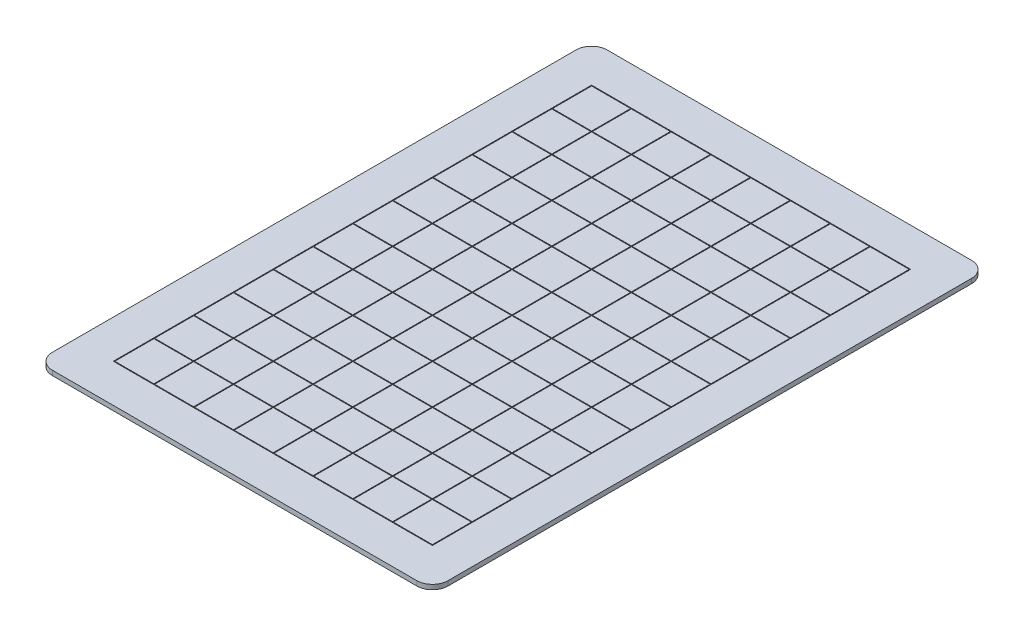
SolidWorks part; units mm, degrees
ref_plane "Front Plane" through (0, 0, 0) normal (0, 0, 1) x (1, 0, 0)
ref_plane "Top Plane" through (0, 0, 0) normal (0, 1, 0) x (1, 0, 0)
ref_plane "Right Plane" through (0, 0, 0) normal (1, 0, 0) x (0, 0, -1)
sketch "Sketch1" plane through (0, 0, 0) normal (0, 1, 0) x (1, 0, 0)
  line L1 (0, 0) -> (253.5, 0)
  line L2 (0, 0) -> (0, 355.5)
  line L3 (0, 355.5) -> (253.5, 355.5)
  line L4 (253.5, 0) -> (253.5, 355.5)
  dimension "D1" = 253.5
  dimension "D2" = 355.5
extrude "Boss-Extrude1" add sketch "Sketch1" along normal blind 3
sketch "Sketch2" plane through (0, 3, 0) normal (0, 1, 0) x (1, 0, 0)
  line L0 (0, 0) -> (253.5, 0) construction
  line L1 (25, 50) -> (50, 50)
  line L2 (25, 50) -> (25, 25)
  line L3 (25, 25) -> (50, 25)
  line L4 (50, 50) -> (50, 25)
  line L5 (0, 355.5) -> (0, 0) construction
  line L6 (50.5, 50) -> (50.5, 25)
  line L7 (50.5, 50) -> (75.5, 50)
  line L8 (75.5, 50) -> (75.5, 25)
  line L9 (50.5, 25) -> (75.5, 25)
  line L10 (76, 50) -> (76, 25)
  line L11 (76, 50) -> (101, 50)
  line L12 (101, 50) -> (101, 25)
  line L13 (76, 25) -> (101, 25)
  line L14 (101.5, 50) -> (101.5, 25)
  line L15 (101.5, 50) -> (126.5, 50)
  line L16 (126.5, 50) -> (126.5, 25)
  line L17 (101.5, 25) -> (126.5, 25)
  line L18 (127, 50) -> (127, 25)
  line L19 (127, 50) -> (152, 50)
  line L20 (152, 50) -> (152, 25)
  line L21 (127, 25) -> (152, 25)
  line L22 (152.5, 50) -> (152.5, 25)
  line L23 (152.5, 50) -> (177.5, 50)
  line L24 (177.5, 50) -> (177.5, 25)
  line L25 (152.5, 25) -> (177.5, 25)
  line L26 (178, 50) -> (178, 25)
  line L27 (178, 50) -> (203, 50)
  line L28 (203, 50) -> (203, 25)
  line L29 (178, 25) -> (203, 25)
  line L30 (203.5, 50) -> (203.5, 25)
  line L31 (203.5, 50) -> (228.5, 50)
  line L32 (228.5, 50) -> (228.5, 25)
  line L33 (203.5, 25) -> (228.5, 25)
  line L34 (50.5, 75.5) -> (50.5, 50.5)
  line L35 (50.5, 75.5) -> (75.5, 75.5)
  line L36 (75.5, 75.5) -> (75.5, 50.5)
  line L37 (50.5, 50.5) -> (75.5, 50.5)
  line L38 (76, 75.5) -> (76, 50.5)
  line L39 (76, 75.5) -> (101, 75.5)
  line L40 (101, 75.5) -> (101, 50.5)
  line L41 (76, 50.5) -> (101, 50.5)
  line L42 (101.5, 75.5) -> (101.5, 50.5)
  line L43 (101.5, 75.5) -> (126.5, 75.5)
  line L44 (126.5, 75.5) -> (126.5, 50.5)
  line L45 (101.5, 50.5) -> (126.5, 50.5)
  line L46 (127, 75.5) -> (127, 50.5)
  line L47 (127, 75.5) -> (152, 75.5)
  line L48 (152, 75.5) -> (152, 50.5)
  line L49 (127, 50.5) -> (152, 50.5)
  line L50 (152.5, 75.5) -> (152.5, 50.5)
  line L51 (152.5, 75.5) -> (177.5, 75.5)
  line L52 (177.5, 75.5) -> (177.5, 50.5)
  line L53 (152.5, 50.5) -> (177.5, 50.5)
  line L54 (178, 75.5) -> (178, 50.5)
  line L55 (178, 75.5) -> (203, 75.5)
  line L56 (203, 75.5) -> (203, 50.5)
  line L57 (178, 50.5) -> (203, 50.5)
  line L58 (203.5, 75.5) -> (203.5, 50.5)
  line L59 (203.5, 75.5) -> (228.5, 75.5)
  line L60 (228.5, 75.5) -> (228.5, 50.5)
  line L61 (203.5, 50.5) -> (228.5, 50.5)
  line L62 (50.5, 101) -> (50.5, 76)
  line L63 (50.5, 101) -> (75.5, 101)
  line L64 (75.5, 101) -> (75.5, 76)
  line L65 (50.5, 76) -> (75.5, 76)
  line L66 (76, 101) -> (76, 76)
  line L67 (76, 101) -> (101, 101)
  line L68 (101, 101) -> (101, 76)
  line L69 (76, 76) -> (101, 76)
  line L70 (101.5, 101) -> (101.5, 76)
  line L71 (101.5, 101) -> (126.5, 101)
  line L72 (126.5, 101) -> (126.5, 76)
  line L73 (101.5, 76) -> (126.5, 76)
  line L74 (127, 101) -> (127, 76)
  line L75 (127, 101) -> (152, 101)
  line L76 (152, 101) -> (152, 76)
  line L77 (127, 76) -> (152, 76)
  line L78 (152.5, 101) -> (152.5, 76)
  line L79 (152.5, 101) -> (177.5, 101)
  line L80 (177.5, 101) -> (177.5, 76)
  line L81 (152.5, 76) -> (177.5, 76)
  line L82 (178, 101) -> (178, 76)
  line L83 (178, 101) -> (203, 101)
  line L84 (203, 101) -> (203, 76)
  line L85 (178, 76) -> (203, 76)
  line L86 (203.5, 101) -> (203.5, 76)
  line L87 (203.5, 101) -> (228.5, 101)
  line L88 (228.5, 101) -> (228.5, 76)
  line L89 (203.5, 76) -> (228.5, 76)
  line L90 (50.5, 126.5) -> (50.5, 101.5)
  line L91 (50.5, 126.5) -> (75.5, 126.5)
  line L92 (75.5, 126.5) -> (75.5, 101.5)
  line L93 (50.5, 101.5) -> (75.5, 101.5)
  line L94 (76, 126.5) -> (76, 101.5)
  line L95 (76, 126.5) -> (101, 126.5)
  line L96 (101, 126.5) -> (101, 101.5)
  line L97 (76, 101.5) -> (101, 101.5)
  line L98 (101.5, 126.5) -> (101.5, 101.5)
  line L99 (101.5, 126.5) -> (126.5, 126.5)
  line L100 (126.5, 126.5) -> (126.5, 101.5)
  line L101 (101.5, 101.5) -> (126.5, 101.5)
  line L102 (127, 126.5) -> (127, 101.5)
  line L103 (127, 126.5) -> (152, 126.5)
  line L104 (152, 126.5) -> (152, 101.5)
  line L105 (127, 101.5) -> (152, 101.5)
  line L106 (152.5, 126.5) -> (152.5, 101.5)
  line L107 (152.5, 126.5) -> (177.5, 126.5)
  line L108 (177.5, 126.5) -> (177.5, 101.5)
  line L109 (152.5, 101.5) -> (177.5, 101.5)
  line L110 (178, 126.5) -> (178, 101.5)
  line L111 (178, 126.5) -> (203, 126.5)
  line L112 (203, 126.5) -> (203, 101.5)
  line L113 (178, 101.5) -> (203, 101.5)
  line L114 (203.5, 126.5) -> (203.5, 101.5)
  line L115 (203.5, 126.5) -> (228.5, 126.5)
  line L116 (228.5, 126.5) -> (228.5, 101.5)
  line L117 (203.5, 101.5) -> (228.5, 101.5)
  line L118 (50.5, 152) -> (50.5, 127)
  line L119 (50.5, 152) -> (75.5, 152)
  line L120 (75.5, 152) -> (75.5, 127)
  line L121 (50.5, 127) -> (75.5, 127)
  line L122 (76, 152) -> (76, 127)
  line L123 (76, 152) -> (101, 152)
  line L124 (101, 152) -> (101, 127)
  line L125 (76, 127) -> (101, 127)
  line L126 (101.5, 152) -> (101.5, 127)
  line L127 (101.5, 152) -> (126.5, 152)
  line L128 (126.5, 152) -> (126.5, 127)
  line L129 (101.5, 127) -> (126.5, 127)
  line L130 (127, 152) -> (127, 127)
  line L131 (127, 152) -> (152, 152)
  line L132 (152, 152) -> (152, 127)
  line L133 (127, 127) -> (152, 127)
  line L134 (152.5, 152) -> (152.5, 127)
  line L135 (152.5, 152) -> (177.5, 152)
  line L136 (177.5, 152) -> (177.5, 127)
  line L137 (152.5, 127) -> (177.5, 127)
  line L138 (178, 152) -> (178, 127)
  line L139 (178, 152) -> (203, 152)
  line L140 (203, 152) -> (203, 127)
  line L141 (178, 127) -> (203, 127)
  line L142 (203.5, 152) -> (203.5, 127)
  line L143 (203.5, 152) -> (228.5, 152)
  line L144 (228.5, 152) -> (228.5, 127)
  line L145 (203.5, 127) -> (228.5, 127)
  line L146 (50.5, 177.5) -> (50.5, 152.5)
  line L147 (50.5, 177.5) -> (75.5, 177.5)
  line L148 (75.5, 177.5) -> (75.5, 152.5)
  line L149 (50.5, 152.5) -> (75.5, 152.5)
  line L150 (76, 177.5) -> (76, 152.5)
  line L151 (76, 177.5) -> (101, 177.5)
  line L152 (101, 177.5) -> (101, 152.5)
  line L153 (76, 152.5) -> (101, 152.5)
  line L154 (101.5, 177.5) -> (101.5, 152.5)
  line L155 (101.5, 177.5) -> (126.5, 177.5)
  line L156 (126.5, 177.5) -> (126.5, 152.5)
  line L157 (101.5, 152.5) -> (126.5, 152.5)
  line L158 (127, 177.5) -> (127, 152.5)
  line L159 (127, 177.5) -> (152, 177.5)
  line L160 (152, 177.5) -> (152, 152.5)
  line L161 (127, 152.5) -> (152, 152.5)
  line L162 (152.5, 177.5) -> (152.5, 152.5)
  line L163 (152.5, 177.5) -> (177.5, 177.5)
  line L164 (177.5, 177.5) -> (177.5, 152.5)
  line L165 (152.5, 152.5) -> (177.5, 152.5)
  line L166 (178, 177.5) -> (178, 152.5)
  line L167 (178, 177.5) -> (203, 177.5)
  line L168 (203, 177.5) -> (203, 152.5)
  line L169 (178, 152.5) -> (203, 152.5)
  line L170 (203.5, 177.5) -> (203.5, 152.5)
  line L171 (203.5, 177.5) -> (228.5, 177.5)
  line L172 (228.5, 177.5) -> (228.5, 152.5)
  line L173 (203.5, 152.5) -> (228.5, 152.5)
  line L174 (50.5, 203) -> (50.5, 178)
  line L175 (50.5, 203) -> (75.5, 203)
  line L176 (75.5, 203) -> (75.5, 178)
  line L177 (50.5, 178) -> (75.5, 178)
  line L178 (76, 203) -> (76, 178)
  line L179 (76, 203) -> (101, 203)
  line L180 (101, 203) -> (101, 178)
  line L181 (76, 178) -> (101, 178)
  line L182 (101.5, 203) -> (101.5, 178)
  line L183 (101.5, 203) -> (126.5, 203)
  line L184 (126.5, 203) -> (126.5, 178)
  line L185 (101.5, 178) -> (126.5, 178)
  line L186 (127, 203) -> (127, 178)
  line L187 (127, 203) -> (152, 203)
  line L188 (152, 203) -> (152, 178)
  line L189 (127, 178) -> (152, 178)
  line L190 (152.5, 203) -> (152.5, 178)
  line L191 (152.5, 203) -> (177.5, 203)
  line L192 (177.5, 203) -> (177.5, 178)
  line L193 (152.5, 178) -> (177.5, 178)
  line L194 (178, 203) -> (178, 178)
  line L195 (178, 203) -> (203, 203)
  line L196 (203, 203) -> (203, 178)
  line L197 (178, 178) -> (203, 178)
  line L198 (203.5, 203) -> (203.5, 178)
  line L199 (203.5, 203) -> (228.5, 203)
  line L200 (228.5, 203) -> (228.5, 178)
  line L201 (203.5, 178) -> (228.5, 178)
  line L202 (50.5, 228.5) -> (50.5, 203.5)
  line L203 (50.5, 228.5) -> (75.5, 228.5)
  line L204 (75.5, 228.5) -> (75.5, 203.5)
  line L205 (50.5, 203.5) -> (75.5, 203.5)
  line L206 (76, 228.5) -> (76, 203.5)
  line L207 (76, 228.5) -> (101, 228.5)
  line L208 (101, 228.5) -> (101, 203.5)
  line L209 (76, 203.5) -> (101, 203.5)
  line L210 (101.5, 228.5) -> (101.5, 203.5)
  line L211 (101.5, 228.5) -> (126.5, 228.5)
  line L212 (126.5, 228.5) -> (126.5, 203.5)
  line L213 (101.5, 203.5) -> (126.5, 203.5)
  line L214 (127, 228.5) -> (127, 203.5)
  line L215 (127, 228.5) -> (152, 228.5)
  line L216 (152, 228.5) -> (152, 203.5)
  line L217 (127, 203.5) -> (152, 203.5)
  line L218 (152.5, 228.5) -> (152.5, 203.5)
  line L219 (152.5, 228.5) -> (177.5, 228.5)
  line L220 (177.5, 228.5) -> (177.5, 203.5)
  line L221 (152.5, 203.5) -> (177.5, 203.5)
  line L222 (178, 228.5) -> (178, 203.5)
  line L223 (178, 228.5) -> (203, 228.5)
  line L224 (203, 228.5) -> (203, 203.5)
  line L225 (178, 203.5) -> (203, 203.5)
  line L226 (203.5, 228.5) -> (203.5, 203.5)
  line L227 (203.5, 228.5) -> (228.5, 228.5)
  line L228 (228.5, 228.5) -> (228.5, 203.5)
  line L229 (203.5, 203.5) -> (228.5, 203.5)
  line L230 (50.5, 254) -> (50.5, 229)
  line L231 (50.5, 254) -> (75.5, 254)
  line L232 (75.5, 254) -> (75.5, 229)
  line L233 (50.5, 229) -> (75.5, 229)
  line L234 (76, 254) -> (76, 229)
  line L235 (76, 254) -> (101, 254)
  line L236 (101, 254) -> (101, 229)
  line L237 (76, 229) -> (101, 229)
  line L238 (101.5, 254) -> (101.5, 229)
  line L239 (101.5, 254) -> (126.5, 254)
  line L240 (126.5, 254) -> (126.5, 229)
  line L241 (101.5, 229) -> (126.5, 229)
  line L242 (127, 254) -> (127, 229)
  line L243 (127, 254) -> (152, 254)
  line L244 (152, 254) -> (152, 229)
  line L245 (127, 229) -> (152, 229)
  line L246 (152.5, 254) -> (152.5, 229)
  line L247 (152.5, 254) -> (177.5, 254)
  line L248 (177.5, 254) -> (177.5, 229)
  line L249 (152.5, 229) -> (177.5, 229)
  line L250 (178, 254) -> (178, 229)
  line L251 (178, 254) -> (203, 254)
  line L252 (203, 254) -> (203, 229)
  line L253 (178, 229) -> (203, 229)
  line L254 (203.5, 254) -> (203.5, 229)
  line L255 (203.5, 254) -> (228.5, 254)
  line L256 (228.5, 254) -> (228.5, 229)
  line L257 (203.5, 229) -> (228.5, 229)
  line L258 (50.5, 279.5) -> (50.5, 254.5)
  line L259 (50.5, 279.5) -> (75.5, 279.5)
  line L260 (75.5, 279.5) -> (75.5, 254.5)
  line L261 (50.5, 254.5) -> (75.5, 254.5)
  line L262 (76, 279.5) -> (76, 254.5)
  line L263 (76, 279.5) -> (101, 279.5)
  line L264 (101, 279.5) -> (101, 254.5)
  line L265 (76, 254.5) -> (101, 254.5)
  line L266 (101.5, 279.5) -> (101.5, 254.5)
  line L267 (101.5, 279.5) -> (126.5, 279.5)
  line L268 (126.5, 279.5) -> (126.5, 254.5)
  line L269 (101.5, 254.5) -> (126.5, 254.5)
  line L270 (127, 279.5) -> (127, 254.5)
  line L271 (127, 279.5) -> (152, 279.5)
  line L272 (152, 279.5) -> (152, 254.5)
  line L273 (127, 254.5) -> (152, 254.5)
  line L274 (152.5, 279.5) -> (152.5, 254.5)
  line L275 (152.5, 279.5) -> (177.5, 279.5)
  line L276 (177.5, 279.5) -> (177.5, 254.5)
  line L277 (152.5, 254.5) -> (177.5, 254.5)
  line L278 (178, 279.5) -> (178, 254.5)
  line L279 (178, 279.5) -> (203, 279.5)
  line L280 (203, 279.5) -> (203, 254.5)
  line L281 (178, 254.5) -> (203, 254.5)
  line L282 (203.5, 279.5) -> (203.5, 254.5)
  line L283 (203.5, 279.5) -> (228.5, 279.5)
  line L284 (228.5, 279.5) -> (228.5, 254.5)
  line L285 (203.5, 254.5) -> (228.5, 254.5)
  line L286 (50.5, 305) -> (50.5, 280)
  line L287 (50.5, 305) -> (75.5, 305)
  line L288 (75.5, 305) -> (75.5, 280)
  line L289 (50.5, 280) -> (75.5, 280)
  line L290 (76, 305) -> (76, 280)
  line L291 (76, 305) -> (101, 305)
  line L292 (101, 305) -> (101, 280)
  line L293 (76, 280) -> (101, 280)
  line L294 (101.5, 305) -> (101.5, 280)
  line L295 (101.5, 305) -> (126.5, 305)
  line L296 (126.5, 305) -> (126.5, 280)
  line L297 (101.5, 280) -> (126.5, 280)
  line L298 (127, 305) -> (127, 280)
  line L299 (127, 305) -> (152, 305)
  line L300 (152, 305) -> (152, 280)
  line L301 (127, 280) -> (152, 280)
  line L302 (152.5, 305) -> (152.5, 280)
  line L303 (152.5, 305) -> (177.5, 305)
  line L304 (177.5, 305) -> (177.5, 280)
  line L305 (152.5, 280) -> (177.5, 280)
  line L306 (178, 305) -> (178, 280)
  line L307 (178, 305) -> (203, 305)
  line L308 (203, 305) -> (203, 280)
  line L309 (178, 280) -> (203, 280)
  line L310 (203.5, 305) -> (203.5, 280)
  line L311 (203.5, 305) -> (228.5, 305)
  line L312 (228.5, 305) -> (228.5, 280)
  line L313 (203.5, 280) -> (228.5, 280)
  line L314 (50.5, 330.5) -> (50.5, 305.5)
  line L315 (50.5, 330.5) -> (75.5, 330.5)
  line L316 (75.5, 330.5) -> (75.5, 305.5)
  line L317 (50.5, 305.5) -> (75.5, 305.5)
  line L318 (76, 330.5) -> (76, 305.5)
  line L319 (76, 330.5) -> (101, 330.5)
  line L320 (101, 330.5) -> (101, 305.5)
  line L321 (76, 305.5) -> (101, 305.5)
  line L322 (101.5, 330.5) -> (101.5, 305.5)
  line L323 (101.5, 330.5) -> (126.5, 330.5)
  line L324 (126.5, 330.5) -> (126.5, 305.5)
  line L325 (101.5, 305.5) -> (126.5, 305.5)
  line L326 (127, 330.5) -> (127, 305.5)
  line L327 (127, 330.5) -> (152, 330.5)
  line L328 (152, 330.5) -> (152, 305.5)
  line L329 (127, 305.5) -> (152, 305.5)
  line L330 (152.5, 330.5) -> (152.5, 305.5)
  line L331 (152.5, 330.5) -> (177.5, 330.5)
  line L332 (177.5, 330.5) -> (177.5, 305.5)
  line L333 (152.5, 305.5) -> (177.5, 305.5)
  line L334 (178, 330.5) -> (178, 305.5)
  line L335 (178, 330.5) -> (203, 330.5)
  line L336 (203, 330.5) -> (203, 305.5)
  line L337 (178, 305.5) -> (203, 305.5)
  line L338 (203.5, 330.5) -> (203.5, 305.5)
  line L339 (203.5, 330.5) -> (228.5, 330.5)
  line L340 (228.5, 330.5) -> (228.5, 305.5)
  line L341 (203.5, 305.5) -> (228.5, 305.5)
  line L342 (25, 75.5) -> (25, 50.5)
  line L343 (25, 75.5) -> (50, 75.5)
  line L344 (50, 75.5) -> (50, 50.5)
  line L345 (25, 50.5) -> (50, 50.5)
  line L346 (25, 101) -> (25, 76)
  line L347 (25, 101) -> (50, 101)
  line L348 (50, 101) -> (50, 76)
  line L349 (25, 76) -> (50, 76)
  line L350 (25, 126.5) -> (25, 101.5)
  line L351 (25, 126.5) -> (50, 126.5)
  line L352 (50, 126.5) -> (50, 101.5)
  line L353 (25, 101.5) -> (50, 101.5)
  line L354 (25, 152) -> (25, 127)
  line L355 (25, 152) -> (50, 152)
  line L356 (50, 152) -> (50, 127)
  line L357 (25, 127) -> (50, 127)
  line L358 (25, 177.5) -> (25, 152.5)
  line L359 (25, 177.5) -> (50, 177.5)
  line L360 (50, 177.5) -> (50, 152.5)
  line L361 (25, 152.5) -> (50, 152.5)
  line L362 (25, 203) -> (25, 178)
  line L363 (25, 203) -> (50, 203)
  line L364 (50, 203) -> (50, 178)
  line L365 (25, 178) -> (50, 178)
  line L366 (25, 228.5) -> (25, 203.5)
  line L367 (25, 228.5) -> (50, 228.5)
  line L368 (50, 228.5) -> (50, 203.5)
  line L369 (25, 203.5) -> (50, 203.5)
  line L370 (25, 254) -> (25, 229)
  line L371 (25, 254) -> (50, 254)
  line L372 (50, 254) -> (50, 229)
  line L373 (25, 229) -> (50, 229)
  line L374 (25, 279.5) -> (25, 254.5)
  line L375 (25, 279.5) -> (50, 279.5)
  line L376 (50, 279.5) -> (50, 254.5)
  line L377 (25, 254.5) -> (50, 254.5)
  line L378 (25, 305) -> (25, 280)
  line L379 (25, 305) -> (50, 305)
  line L380 (50, 305) -> (50, 280)
  line L381 (25, 280) -> (50, 280)
  line L382 (25, 330.5) -> (25, 305.5)
  line L383 (25, 330.5) -> (50, 330.5)
  line L384 (50, 330.5) -> (50, 305.5)
  line L385 (25, 305.5) -> (50, 305.5)
  line L387 (24.5, 331) -> (229, 331)
  line L388 (24.5, 331) -> (24.5, 24.5)
  line L389 (24.5, 24.5) -> (229, 24.5)
  line L390 (229, 331) -> (229, 24.5)
  dimension "D1" = 25
  dimension "D2" = 25
  dimension "D3" = 25
  dimension "D4" = 25
  dimension "D7" = 0.5
  dimension "D8" = 0.5
  dimension "D9" = 0.5
  dimension "D10" = 0.5
  dimension "D11" = 0.5
  dimension "D5" = 8
  dimension "D6" = 12
extrude "Cut-Extrude1" cut sketch "Sketch2" against normal blind 0.5
sketch "Sketch4" plane through (0, 0, 0) normal (0, -1, 0) x (1, 0, 0)
  line L0 (0, -355.5) -> (0, 0) construction
  line L1 (0, 0) -> (253.5, 0) construction
  line L2 (253.5, -355.5) -> (0, -355.5) construction
  line L3 (0, 0) -> (253.5, 0)
  line L4 (253.5, -355.5) -> (0, -355.5)
  line L5 (126.75, -355.5) -> (126.75, 0)
  line L6 (253.5, 0) -> (253.5, -355.5) construction
  line L7 (0, -355.5) -> (0, 0) construction
  line L8 (253.5, 0) -> (253.5, -355.5)
  line L9 (0, -355.5) -> (0, 0)
  line L10 (0, -177.75) -> (253.5, -177.75)
  circle A0 centre (6, -6) radius 1.6
  circle A1 centre (6, -91.875) radius 1.6
  circle A2 centre (6, -177.75) radius 1.6
  circle A3 centre (6, -263.625) radius 1.6
  circle A4 centre (6, -349.5) radius 1.6
  circle A5 centre (247.5, -6) radius 1.6
  circle A6 centre (247.5, -91.875) radius 1.6
  circle A7 centre (247.5, -177.75) radius 1.6
  circle A8 centre (247.5, -263.625) radius 1.6
  circle A10 centre (86.5, -349.5) radius 1.6
  circle A11 centre (167, -349.5) radius 1.6
  circle A12 centre (247.5, -349.5) radius 1.6
  circle A13 centre (167, -6) radius 1.6
  circle A14 centre (86.5, -6) radius 1.6
  dimension "D1" = 3.2
  dimension "D2" = 6
  dimension "D3" = 6
  dimension "D5" = 6
  dimension "D7" = 6
  dimension "D4" = 5
  dimension "D6" = 4
extrude "Cut-Extrude2" cut sketch "Sketch4" against normal blind 1.2 contours A14 | A0 | A13 | A5 | A6 | A7 L10 | A7 L10 | A8 | A12 | A11 | A10 | A4 | A3 | L10 A2 | L10 A2 | A1 region at (6, 0, -177.0709) region at (6, 0, -178.4291) region at (247.5, 0, -177.0709) region at (247.5, 0, -178.4291) region at (6, 0, -6) region at (6, 0, -91.875) region at (6, 0, -263.625) region at (6, 0, -349.5) region at (247.5, 0, -6) region at (247.5, 0, -91.875) region at (247.5, 0, -263.625) region at (86.5, 0, -349.5) region at (167, 0, -349.5) region at (247.5, 0, -349.5) region at (167, 0, -6) region at (86.5, 0, -6)
fillet "Fillet1" radius 10 4 edges at (253.5, 1.5, 0) (0, 1.5, 0) (0, 1.5, -355.5) (253.5, 1.5, -355.5)
sketch "Sketch5" plane through (0, 0, 0) normal (0, -1, 0) x (1, 0, 0)
  line L1 (218.5, -265) -> (213.5, -265)
  line L2 (218.5, -265) -> (218.5, -269)
  line L3 (218.5, -269) -> (213.5, -269)
  line L4 (213.5, -265) -> (213.5, -269)
  line L6 (216, -265) -> (216, -269)
  line L9 (203.5, -279.5) -> (203.5, -254.5) construction
  line L10 (228.5, -279.5) -> (203.5, -279.5) construction
  line L11 (216, -271) -> (216, -275.38)
  line L12 (218.5, -271) -> (213.5, -271)
  line L13 (218.5, -271) -> (218.5, -275.38)
  line L14 (218.5, -275.38) -> (213.5, -275.38)
  line L15 (213.5, -271) -> (213.5, -275.38)
  line L16 (193, -265) -> (193, -269)
  line L17 (193, -265) -> (188, -265)
  line L18 (188, -265) -> (188, -269)
  line L19 (193, -269) -> (188, -269)
  line L20 (193, -271) -> (193, -275.38)
  line L21 (193, -271) -> (188, -271)
  line L22 (188, -271) -> (188, -275.38)
  line L23 (193, -275.38) -> (188, -275.38)
  line L24 (167.5, -265) -> (167.5, -269)
  line L25 (167.5, -265) -> (162.5, -265)
  line L26 (162.5, -265) -> (162.5, -269)
  line L27 (167.5, -269) -> (162.5, -269)
  line L28 (167.5, -271) -> (167.5, -275.38)
  line L29 (167.5, -271) -> (162.5, -271)
  line L30 (162.5, -271) -> (162.5, -275.38)
  line L31 (167.5, -275.38) -> (162.5, -275.38)
  line L32 (142, -265) -> (142, -269)
  line L33 (142, -265) -> (137, -265)
  line L34 (137, -265) -> (137, -269)
  line L35 (142, -269) -> (137, -269)
  line L36 (142, -271) -> (142, -275.38)
  line L37 (142, -271) -> (137, -271)
  line L38 (137, -271) -> (137, -275.38)
  line L39 (142, -275.38) -> (137, -275.38)
  line L40 (116.5, -265) -> (116.5, -269)
  line L41 (116.5, -265) -> (111.5, -265)
  line L42 (111.5, -265) -> (111.5, -269)
  line L43 (116.5, -269) -> (111.5, -269)
  line L44 (116.5, -271) -> (116.5, -275.38)
  line L45 (116.5, -271) -> (111.5, -271)
  line L46 (111.5, -271) -> (111.5, -275.38)
  line L47 (116.5, -275.38) -> (111.5, -275.38)
  line L48 (91, -265) -> (91, -269)
  line L49 (91, -265) -> (86, -265)
  line L50 (86, -265) -> (86, -269)
  line L51 (91, -269) -> (86, -269)
  line L52 (91, -271) -> (91, -275.38)
  line L53 (91, -271) -> (86, -271)
  line L54 (86, -271) -> (86, -275.38)
  line L55 (91, -275.38) -> (86, -275.38)
  line L56 (65.5, -265) -> (65.5, -269)
  line L57 (65.5, -265) -> (60.5, -265)
  line L58 (60.5, -265) -> (60.5, -269)
  line L59 (65.5, -269) -> (60.5, -269)
  line L60 (65.5, -271) -> (65.5, -275.38)
  line L61 (65.5, -271) -> (60.5, -271)
  line L62 (60.5, -271) -> (60.5, -275.38)
  line L63 (65.5, -275.38) -> (60.5, -275.38)
  line L64 (40, -265) -> (40, -269)
  line L65 (40, -265) -> (35, -265)
  line L66 (35, -265) -> (35, -269)
  line L67 (40, -269) -> (35, -269)
  line L68 (40, -271) -> (40, -275.38)
  line L69 (40, -271) -> (35, -271)
  line L70 (35, -271) -> (35, -275.38)
  line L71 (40, -275.38) -> (35, -275.38)
  line L72 (193, -239.5) -> (193, -243.5)
  line L73 (193, -239.5) -> (188, -239.5)
  line L74 (188, -239.5) -> (188, -243.5)
  line L75 (193, -243.5) -> (188, -243.5)
  line L76 (193, -245.5) -> (193, -249.88)
  line L77 (193, -245.5) -> (188, -245.5)
  line L78 (188, -245.5) -> (188, -249.88)
  line L79 (193, -249.88) -> (188, -249.88)
  line L80 (167.5, -239.5) -> (167.5, -243.5)
  line L81 (167.5, -239.5) -> (162.5, -239.5)
  line L82 (162.5, -239.5) -> (162.5, -243.5)
  line L83 (167.5, -243.5) -> (162.5, -243.5)
  line L84 (167.5, -245.5) -> (167.5, -249.88)
  line L85 (167.5, -245.5) -> (162.5, -245.5)
  line L86 (162.5, -245.5) -> (162.5, -249.88)
  line L87 (167.5, -249.88) -> (162.5, -249.88)
  line L88 (142, -239.5) -> (142, -243.5)
  line L89 (142, -239.5) -> (137, -239.5)
  line L90 (137, -239.5) -> (137, -243.5)
  line L91 (142, -243.5) -> (137, -243.5)
  line L92 (142, -245.5) -> (142, -249.88)
  line L93 (142, -245.5) -> (137, -245.5)
  line L94 (137, -245.5) -> (137, -249.88)
  line L95 (142, -249.88) -> (137, -249.88)
  line L96 (116.5, -239.5) -> (116.5, -243.5)
  line L97 (116.5, -239.5) -> (111.5, -239.5)
  line L98 (111.5, -239.5) -> (111.5, -243.5)
  line L99 (116.5, -243.5) -> (111.5, -243.5)
  line L100 (116.5, -245.5) -> (116.5, -249.88)
  line L101 (116.5, -245.5) -> (111.5, -245.5)
  line L102 (111.5, -245.5) -> (111.5, -249.88)
  line L103 (116.5, -249.88) -> (111.5, -249.88)
  line L104 (91, -239.5) -> (91, -243.5)
  line L105 (91, -239.5) -> (86, -239.5)
  line L106 (86, -239.5) -> (86, -243.5)
  line L107 (91, -243.5) -> (86, -243.5)
  line L108 (91, -245.5) -> (91, -249.88)
  line L109 (91, -245.5) -> (86, -245.5)
  line L110 (86, -245.5) -> (86, -249.88)
  line L111 (91, -249.88) -> (86, -249.88)
  line L112 (65.5, -239.5) -> (65.5, -243.5)
  line L113 (65.5, -239.5) -> (60.5, -239.5)
  line L114 (60.5, -239.5) -> (60.5, -243.5)
  line L115 (65.5, -243.5) -> (60.5, -243.5)
  line L116 (65.5, -245.5) -> (65.5, -249.88)
  line L117 (65.5, -245.5) -> (60.5, -245.5)
  line L118 (60.5, -245.5) -> (60.5, -249.88)
  line L119 (65.5, -249.88) -> (60.5, -249.88)
  line L120 (40, -239.5) -> (40, -243.5)
  line L121 (40, -239.5) -> (35, -239.5)
  line L122 (35, -239.5) -> (35, -243.5)
  line L123 (40, -243.5) -> (35, -243.5)
  line L124 (40, -245.5) -> (40, -249.88)
  line L125 (40, -245.5) -> (35, -245.5)
  line L126 (35, -245.5) -> (35, -249.88)
  line L127 (40, -249.88) -> (35, -249.88)
  line L128 (193, -214) -> (193, -218)
  line L129 (193, -214) -> (188, -214)
  line L130 (188, -214) -> (188, -218)
  line L131 (193, -218) -> (188, -218)
  line L132 (193, -220) -> (193, -224.38)
  line L133 (193, -220) -> (188, -220)
  line L134 (188, -220) -> (188, -224.38)
  line L135 (193, -224.38) -> (188, -224.38)
  line L136 (167.5, -214) -> (167.5, -218)
  line L137 (167.5, -214) -> (162.5, -214)
  line L138 (162.5, -214) -> (162.5, -218)
  line L139 (167.5, -218) -> (162.5, -218)
  line L140 (167.5, -220) -> (167.5, -224.38)
  line L141 (167.5, -220) -> (162.5, -220)
  line L142 (162.5, -220) -> (162.5, -224.38)
  line L143 (167.5, -224.38) -> (162.5, -224.38)
  line L144 (142, -214) -> (142, -218)
  line L145 (142, -214) -> (137, -214)
  line L146 (137, -214) -> (137, -218)
  line L147 (142, -218) -> (137, -218)
  line L148 (142, -220) -> (142, -224.38)
  line L149 (142, -220) -> (137, -220)
  line L150 (137, -220) -> (137, -224.38)
  line L151 (142, -224.38) -> (137, -224.38)
  line L152 (116.5, -214) -> (116.5, -218)
  line L153 (116.5, -214) -> (111.5, -214)
  line L154 (111.5, -214) -> (111.5, -218)
  line L155 (116.5, -218) -> (111.5, -218)
  line L156 (116.5, -220) -> (116.5, -224.38)
  line L157 (116.5, -220) -> (111.5, -220)
  line L158 (111.5, -220) -> (111.5, -224.38)
  line L159 (116.5, -224.38) -> (111.5, -224.38)
  line L160 (91, -214) -> (91, -218)
  line L161 (91, -214) -> (86, -214)
  line L162 (86, -214) -> (86, -218)
  line L163 (91, -218) -> (86, -218)
  line L164 (91, -220) -> (91, -224.38)
  line L165 (91, -220) -> (86, -220)
  line L166 (86, -220) -> (86, -224.38)
  line L167 (91, -224.38) -> (86, -224.38)
  line L168 (65.5, -214) -> (65.5, -218)
  line L169 (65.5, -214) -> (60.5, -214)
  line L170 (60.5, -214) -> (60.5, -218)
  line L171 (65.5, -218) -> (60.5, -218)
  line L172 (65.5, -220) -> (65.5, -224.38)
  line L173 (65.5, -220) -> (60.5, -220)
  line L174 (60.5, -220) -> (60.5, -224.38)
  line L175 (65.5, -224.38) -> (60.5, -224.38)
  line L176 (40, -214) -> (40, -218)
  line L177 (40, -214) -> (35, -214)
  line L178 (35, -214) -> (35, -218)
  line L179 (40, -218) -> (35, -218)
  line L180 (40, -220) -> (40, -224.38)
  line L181 (40, -220) -> (35, -220)
  line L182 (35, -220) -> (35, -224.38)
  line L183 (40, -224.38) -> (35, -224.38)
  line L184 (193, -188.5) -> (193, -192.5)
  line L185 (193, -188.5) -> (188, -188.5)
  line L186 (188, -188.5) -> (188, -192.5)
  line L187 (193, -192.5) -> (188, -192.5)
  line L188 (193, -194.5) -> (193, -198.88)
  line L189 (193, -194.5) -> (188, -194.5)
  line L190 (188, -194.5) -> (188, -198.88)
  line L191 (193, -198.88) -> (188, -198.88)
  line L192 (167.5, -188.5) -> (167.5, -192.5)
  line L193 (167.5, -188.5) -> (162.5, -188.5)
  line L194 (162.5, -188.5) -> (162.5, -192.5)
  line L195 (167.5, -192.5) -> (162.5, -192.5)
  line L196 (167.5, -194.5) -> (167.5, -198.88)
  line L197 (167.5, -194.5) -> (162.5, -194.5)
  line L198 (162.5, -194.5) -> (162.5, -198.88)
  line L199 (167.5, -198.88) -> (162.5, -198.88)
  line L200 (142, -188.5) -> (142, -192.5)
  line L201 (142, -188.5) -> (137, -188.5)
  line L202 (137, -188.5) -> (137, -192.5)
  line L203 (142, -192.5) -> (137, -192.5)
  line L204 (142, -194.5) -> (142, -198.88)
  line L205 (142, -194.5) -> (137, -194.5)
  line L206 (137, -194.5) -> (137, -198.88)
  line L207 (142, -198.88) -> (137, -198.88)
  line L208 (116.5, -188.5) -> (116.5, -192.5)
  line L209 (116.5, -188.5) -> (111.5, -188.5)
  line L210 (111.5, -188.5) -> (111.5, -192.5)
  line L211 (116.5, -192.5) -> (111.5, -192.5)
  line L212 (116.5, -194.5) -> (116.5, -198.88)
  line L213 (116.5, -194.5) -> (111.5, -194.5)
  line L214 (111.5, -194.5) -> (111.5, -198.88)
  line L215 (116.5, -198.88) -> (111.5, -198.88)
  line L216 (91, -188.5) -> (91, -192.5)
  line L217 (91, -188.5) -> (86, -188.5)
  line L218 (86, -188.5) -> (86, -192.5)
  line L219 (91, -192.5) -> (86, -192.5)
  line L220 (91, -194.5) -> (91, -198.88)
  line L221 (91, -194.5) -> (86, -194.5)
  line L222 (86, -194.5) -> (86, -198.88)
  line L223 (91, -198.88) -> (86, -198.88)
  line L224 (65.5, -188.5) -> (65.5, -192.5)
  line L225 (65.5, -188.5) -> (60.5, -188.5)
  line L226 (60.5, -188.5) -> (60.5, -192.5)
  line L227 (65.5, -192.5) -> (60.5, -192.5)
  line L228 (65.5, -194.5) -> (65.5, -198.88)
  line L229 (65.5, -194.5) -> (60.5, -194.5)
  line L230 (60.5, -194.5) -> (60.5, -198.88)
  line L231 (65.5, -198.88) -> (60.5, -198.88)
  line L232 (40, -188.5) -> (40, -192.5)
  line L233 (40, -188.5) -> (35, -188.5)
  line L234 (35, -188.5) -> (35, -192.5)
  line L235 (40, -192.5) -> (35, -192.5)
  line L236 (40, -194.5) -> (40, -198.88)
  line L237 (40, -194.5) -> (35, -194.5)
  line L238 (35, -194.5) -> (35, -198.88)
  line L239 (40, -198.88) -> (35, -198.88)
  line L240 (193, -163) -> (193, -167)
  line L241 (193, -163) -> (188, -163)
  line L242 (188, -163) -> (188, -167)
  line L243 (193, -167) -> (188, -167)
  line L244 (193, -169) -> (193, -173.38)
  line L245 (193, -169) -> (188, -169)
  line L246 (188, -169) -> (188, -173.38)
  line L247 (193, -173.38) -> (188, -173.38)
  line L248 (167.5, -163) -> (167.5, -167)
  line L249 (167.5, -163) -> (162.5, -163)
  line L250 (162.5, -163) -> (162.5, -167)
  line L251 (167.5, -167) -> (162.5, -167)
  line L252 (167.5, -169) -> (167.5, -173.38)
  line L253 (167.5, -169) -> (162.5, -169)
  line L254 (162.5, -169) -> (162.5, -173.38)
  line L255 (167.5, -173.38) -> (162.5, -173.38)
  line L256 (142, -163) -> (142, -167)
  line L257 (142, -163) -> (137, -163)
  line L258 (137, -163) -> (137, -167)
  line L259 (142, -167) -> (137, -167)
  line L260 (142, -169) -> (142, -173.38)
  line L261 (142, -169) -> (137, -169)
  line L262 (137, -169) -> (137, -173.38)
  line L263 (142, -173.38) -> (137, -173.38)
  line L264 (116.5, -163) -> (116.5, -167)
  line L265 (116.5, -163) -> (111.5, -163)
  line L266 (111.5, -163) -> (111.5, -167)
  line L267 (116.5, -167) -> (111.5, -167)
  line L268 (116.5, -169) -> (116.5, -173.38)
  line L269 (116.5, -169) -> (111.5, -169)
  line L270 (111.5, -169) -> (111.5, -173.38)
  line L271 (116.5, -173.38) -> (111.5, -173.38)
  line L272 (91, -163) -> (91, -167)
  line L273 (91, -163) -> (86, -163)
  line L274 (86, -163) -> (86, -167)
  line L275 (91, -167) -> (86, -167)
  line L276 (91, -169) -> (91, -173.38)
  line L277 (91, -169) -> (86, -169)
  line L278 (86, -169) -> (86, -173.38)
  line L279 (91, -173.38) -> (86, -173.38)
  line L280 (65.5, -163) -> (65.5, -167)
  line L281 (65.5, -163) -> (60.5, -163)
  line L282 (60.5, -163) -> (60.5, -167)
  line L283 (65.5, -167) -> (60.5, -167)
  line L284 (65.5, -169) -> (65.5, -173.38)
  line L285 (65.5, -169) -> (60.5, -169)
  line L286 (60.5, -169) -> (60.5, -173.38)
  line L287 (65.5, -173.38) -> (60.5, -173.38)
  line L288 (40, -163) -> (40, -167)
  line L289 (40, -163) -> (35, -163)
  line L290 (35, -163) -> (35, -167)
  line L291 (40, -167) -> (35, -167)
  line L292 (40, -169) -> (40, -173.38)
  line L293 (40, -169) -> (35, -169)
  line L294 (35, -169) -> (35, -173.38)
  line L295 (40, -173.38) -> (35, -173.38)
  line L296 (193, -137.5) -> (193, -141.5)
  line L297 (193, -137.5) -> (188, -137.5)
  line L298 (188, -137.5) -> (188, -141.5)
  line L299 (193, -141.5) -> (188, -141.5)
  line L300 (193, -143.5) -> (193, -147.88)
  line L301 (193, -143.5) -> (188, -143.5)
  line L302 (188, -143.5) -> (188, -147.88)
  line L303 (193, -147.88) -> (188, -147.88)
  line L304 (167.5, -137.5) -> (167.5, -141.5)
  line L305 (167.5, -137.5) -> (162.5, -137.5)
  line L306 (162.5, -137.5) -> (162.5, -141.5)
  line L307 (167.5, -141.5) -> (162.5, -141.5)
  line L308 (167.5, -143.5) -> (167.5, -147.88)
  line L309 (167.5, -143.5) -> (162.5, -143.5)
  line L310 (162.5, -143.5) -> (162.5, -147.88)
  line L311 (167.5, -147.88) -> (162.5, -147.88)
  line L312 (142, -137.5) -> (142, -141.5)
  line L313 (142, -137.5) -> (137, -137.5)
  line L314 (137, -137.5) -> (137, -141.5)
  line L315 (142, -141.5) -> (137, -141.5)
  line L316 (142, -143.5) -> (142, -147.88)
  line L317 (142, -143.5) -> (137, -143.5)
  line L318 (137, -143.5) -> (137, -147.88)
  line L319 (142, -147.88) -> (137, -147.88)
  line L320 (116.5, -137.5) -> (116.5, -141.5)
  line L321 (116.5, -137.5) -> (111.5, -137.5)
  line L322 (111.5, -137.5) -> (111.5, -141.5)
  line L323 (116.5, -141.5) -> (111.5, -141.5)
  line L324 (116.5, -143.5) -> (116.5, -147.88)
  line L325 (116.5, -143.5) -> (111.5, -143.5)
  line L326 (111.5, -143.5) -> (111.5, -147.88)
  line L327 (116.5, -147.88) -> (111.5, -147.88)
  line L328 (91, -137.5) -> (91, -141.5)
  line L329 (91, -137.5) -> (86, -137.5)
  line L330 (86, -137.5) -> (86, -141.5)
  line L331 (91, -141.5) -> (86, -141.5)
  line L332 (91, -143.5) -> (91, -147.88)
  line L333 (91, -143.5) -> (86, -143.5)
  line L334 (86, -143.5) -> (86, -147.88)
  line L335 (91, -147.88) -> (86, -147.88)
  line L336 (65.5, -137.5) -> (65.5, -141.5)
  line L337 (65.5, -137.5) -> (60.5, -137.5)
  line L338 (60.5, -137.5) -> (60.5, -141.5)
  line L339 (65.5, -141.5) -> (60.5, -141.5)
  line L340 (65.5, -143.5) -> (65.5, -147.88)
  line L341 (65.5, -143.5) -> (60.5, -143.5)
  line L342 (60.5, -143.5) -> (60.5, -147.88)
  line L343 (65.5, -147.88) -> (60.5, -147.88)
  line L344 (40, -137.5) -> (40, -141.5)
  line L345 (40, -137.5) -> (35, -137.5)
  line L346 (35, -137.5) -> (35, -141.5)
  line L347 (40, -141.5) -> (35, -141.5)
  line L348 (40, -143.5) -> (40, -147.88)
  line L349 (40, -143.5) -> (35, -143.5)
  line L350 (35, -143.5) -> (35, -147.88)
  line L351 (40, -147.88) -> (35, -147.88)
  line L352 (193, -112) -> (193, -116)
  line L353 (193, -112) -> (188, -112)
  line L354 (188, -112) -> (188, -116)
  line L355 (193, -116) -> (188, -116)
  line L356 (193, -118) -> (193, -122.38)
  line L357 (193, -118) -> (188, -118)
  line L358 (188, -118) -> (188, -122.38)
  line L359 (193, -122.38) -> (188, -122.38)
  line L360 (167.5, -112) -> (167.5, -116)
  line L361 (167.5, -112) -> (162.5, -112)
  line L362 (162.5, -112) -> (162.5, -116)
  line L363 (167.5, -116) -> (162.5, -116)
  line L364 (167.5, -118) -> (167.5, -122.38)
  line L365 (167.5, -118) -> (162.5, -118)
  line L366 (162.5, -118) -> (162.5, -122.38)
  line L367 (167.5, -122.38) -> (162.5, -122.38)
  line L368 (142, -112) -> (142, -116)
  line L369 (142, -112) -> (137, -112)
  line L370 (137, -112) -> (137, -116)
  line L371 (142, -116) -> (137, -116)
  line L372 (142, -118) -> (142, -122.38)
  line L373 (142, -118) -> (137, -118)
  line L374 (137, -118) -> (137, -122.38)
  line L375 (142, -122.38) -> (137, -122.38)
  line L376 (116.5, -112) -> (116.5, -116)
  line L377 (116.5, -112) -> (111.5, -112)
  line L378 (111.5, -112) -> (111.5, -116)
  line L379 (116.5, -116) -> (111.5, -116)
  line L380 (116.5, -118) -> (116.5, -122.38)
  line L381 (116.5, -118) -> (111.5, -118)
  line L382 (111.5, -118) -> (111.5, -122.38)
  line L383 (116.5, -122.38) -> (111.5, -122.38)
  line L384 (91, -112) -> (91, -116)
  line L385 (91, -112) -> (86, -112)
  line L386 (86, -112) -> (86, -116)
  line L387 (91, -116) -> (86, -116)
  line L388 (91, -118) -> (91, -122.38)
  line L389 (91, -118) -> (86, -118)
  line L390 (86, -118) -> (86, -122.38)
  line L391 (91, -122.38) -> (86, -122.38)
  line L392 (65.5, -112) -> (65.5, -116)
  line L393 (65.5, -112) -> (60.5, -112)
  line L394 (60.5, -112) -> (60.5, -116)
  line L395 (65.5, -116) -> (60.5, -116)
  line L396 (65.5, -118) -> (65.5, -122.38)
  line L397 (65.5, -118) -> (60.5, -118)
  line L398 (60.5, -118) -> (60.5, -122.38)
  line L399 (65.5, -122.38) -> (60.5, -122.38)
  line L400 (40, -112) -> (40, -116)
  line L401 (40, -112) -> (35, -112)
  line L402 (35, -112) -> (35, -116)
  line L403 (40, -116) -> (35, -116)
  line L404 (40, -118) -> (40, -122.38)
  line L405 (40, -118) -> (35, -118)
  line L406 (35, -118) -> (35, -122.38)
  line L407 (40, -122.38) -> (35, -122.38)
  line L408 (193, -86.5) -> (193, -90.5)
  line L409 (193, -86.5) -> (188, -86.5)
  line L410 (188, -86.5) -> (188, -90.5)
  line L411 (193, -90.5) -> (188, -90.5)
  line L412 (193, -92.5) -> (193, -96.88)
  line L413 (193, -92.5) -> (188, -92.5)
  line L414 (188, -92.5) -> (188, -96.88)
  line L415 (193, -96.88) -> (188, -96.88)
  line L416 (167.5, -86.5) -> (167.5, -90.5)
  line L417 (167.5, -86.5) -> (162.5, -86.5)
  line L418 (162.5, -86.5) -> (162.5, -90.5)
  line L419 (167.5, -90.5) -> (162.5, -90.5)
  line L420 (167.5, -92.5) -> (167.5, -96.88)
  line L421 (167.5, -92.5) -> (162.5, -92.5)
  line L422 (162.5, -92.5) -> (162.5, -96.88)
  line L423 (167.5, -96.88) -> (162.5, -96.88)
  line L424 (142, -86.5) -> (142, -90.5)
  line L425 (142, -86.5) -> (137, -86.5)
  line L426 (137, -86.5) -> (137, -90.5)
  line L427 (142, -90.5) -> (137, -90.5)
  line L428 (142, -92.5) -> (142, -96.88)
  line L429 (142, -92.5) -> (137, -92.5)
  line L430 (137, -92.5) -> (137, -96.88)
  line L431 (142, -96.88) -> (137, -96.88)
  line L432 (116.5, -86.5) -> (116.5, -90.5)
  line L433 (116.5, -86.5) -> (111.5, -86.5)
  line L434 (111.5, -86.5) -> (111.5, -90.5)
  line L435 (116.5, -90.5) -> (111.5, -90.5)
  line L436 (116.5, -92.5) -> (116.5, -96.88)
  line L437 (116.5, -92.5) -> (111.5, -92.5)
  line L438 (111.5, -92.5) -> (111.5, -96.88)
  line L439 (116.5, -96.88) -> (111.5, -96.88)
  line L440 (91, -86.5) -> (91, -90.5)
  line L441 (91, -86.5) -> (86, -86.5)
  line L442 (86, -86.5) -> (86, -90.5)
  line L443 (91, -90.5) -> (86, -90.5)
  line L444 (91, -92.5) -> (91, -96.88)
  line L445 (91, -92.5) -> (86, -92.5)
  line L446 (86, -92.5) -> (86, -96.88)
  line L447 (91, -96.88) -> (86, -96.88)
  line L448 (65.5, -86.5) -> (65.5, -90.5)
  line L449 (65.5, -86.5) -> (60.5, -86.5)
  line L450 (60.5, -86.5) -> (60.5, -90.5)
  line L451 (65.5, -90.5) -> (60.5, -90.5)
  line L452 (65.5, -92.5) -> (65.5, -96.88)
  line L453 (65.5, -92.5) -> (60.5, -92.5)
  line L454 (60.5, -92.5) -> (60.5, -96.88)
  line L455 (65.5, -96.88) -> (60.5, -96.88)
  line L456 (40, -86.5) -> (40, -90.5)
  line L457 (40, -86.5) -> (35, -86.5)
  line L458 (35, -86.5) -> (35, -90.5)
  line L459 (40, -90.5) -> (35, -90.5)
  line L460 (40, -92.5) -> (40, -96.88)
  line L461 (40, -92.5) -> (35, -92.5)
  line L462 (35, -92.5) -> (35, -96.88)
  line L463 (40, -96.88) -> (35, -96.88)
  line L464 (218.5, -239.5) -> (218.5, -243.5)
  line L465 (218.5, -239.5) -> (213.5, -239.5)
  line L466 (213.5, -239.5) -> (213.5, -243.5)
  line L467 (218.5, -243.5) -> (213.5, -243.5)
  line L468 (218.5, -245.5) -> (218.5, -249.88)
  line L469 (218.5, -245.5) -> (213.5, -245.5)
  line L470 (213.5, -245.5) -> (213.5, -249.88)
  line L471 (218.5, -249.88) -> (213.5, -249.88)
  line L472 (218.5, -214) -> (218.5, -218)
  line L473 (218.5, -214) -> (213.5, -214)
  line L474 (213.5, -214) -> (213.5, -218)
  line L475 (218.5, -218) -> (213.5, -218)
  line L476 (218.5, -220) -> (218.5, -224.38)
  line L477 (218.5, -220) -> (213.5, -220)
  line L478 (213.5, -220) -> (213.5, -224.38)
  line L479 (218.5, -224.38) -> (213.5, -224.38)
  line L480 (218.5, -188.5) -> (218.5, -192.5)
  line L481 (218.5, -188.5) -> (213.5, -188.5)
  line L482 (213.5, -188.5) -> (213.5, -192.5)
  line L483 (218.5, -192.5) -> (213.5, -192.5)
  line L484 (218.5, -194.5) -> (218.5, -198.88)
  line L485 (218.5, -194.5) -> (213.5, -194.5)
  line L486 (213.5, -194.5) -> (213.5, -198.88)
  line L487 (218.5, -198.88) -> (213.5, -198.88)
  line L488 (218.5, -163) -> (218.5, -167)
  line L489 (218.5, -163) -> (213.5, -163)
  line L490 (213.5, -163) -> (213.5, -167)
  line L491 (218.5, -167) -> (213.5, -167)
  line L492 (218.5, -169) -> (218.5, -173.38)
  line L493 (218.5, -169) -> (213.5, -169)
  line L494 (213.5, -169) -> (213.5, -173.38)
  line L495 (218.5, -173.38) -> (213.5, -173.38)
  line L496 (218.5, -137.5) -> (218.5, -141.5)
  line L497 (218.5, -137.5) -> (213.5, -137.5)
  line L498 (213.5, -137.5) -> (213.5, -141.5)
  line L499 (218.5, -141.5) -> (213.5, -141.5)
  line L500 (218.5, -143.5) -> (218.5, -147.88)
  line L501 (218.5, -143.5) -> (213.5, -143.5)
  line L502 (213.5, -143.5) -> (213.5, -147.88)
  line L503 (218.5, -147.88) -> (213.5, -147.88)
  line L504 (218.5, -112) -> (218.5, -116)
  line L505 (218.5, -112) -> (213.5, -112)
  line L506 (213.5, -112) -> (213.5, -116)
  line L507 (218.5, -116) -> (213.5, -116)
  line L508 (218.5, -118) -> (218.5, -122.38)
  line L509 (218.5, -118) -> (213.5, -118)
  line L510 (213.5, -118) -> (213.5, -122.38)
  line L511 (218.5, -122.38) -> (213.5, -122.38)
  line L512 (218.5, -86.5) -> (218.5, -90.5)
  line L513 (218.5, -86.5) -> (213.5, -86.5)
  line L514 (213.5, -86.5) -> (213.5, -90.5)
  line L515 (218.5, -90.5) -> (213.5, -90.5)
  line L516 (218.5, -92.5) -> (218.5, -96.88)
  line L517 (218.5, -92.5) -> (213.5, -92.5)
  line L518 (213.5, -92.5) -> (213.5, -96.88)
  line L519 (218.5, -96.88) -> (213.5, -96.88)
  point P4 (216, -267)
  dimension "D1" = 5
  dimension "D2" = 4
  dimension "D3" = 12.5
  dimension "D4" = 12.5
  dimension "D5" = 5
  dimension "D6" = 4.38
  dimension "D7" = 0
  dimension "D8" = 2
  dimension "D9" = 8
  dimension "D10" = 8
extrude "Cut-Extrude3" cut sketch "Sketch5" against normal blind 2 contours L415 L412 L413 L414 | L514 L515 L512 L513 | L518 L519 L516 L517 | L410 L411 L408 L409 | L418 L419 L416 L417 | L422 L423 L420 L421 | L426 L427 L424 L425 | L430 L431 L428 L429 | L434 L435 L432 L433 | L438 L439 L436 L437 | L442 L443 L440 L441 | L446 L447 L444 L445 | L450 L451 L448 L449 | L454 L455 L452 L453 | L458 L459 L456 L457 | L462 L463 L460 L461 | L506 L507 L504 L505 | L510 L511 L508 L509 | L354 L355 L352 L353 | L358 L359 L356 L357 | L362 L363 L360 L361 | L366 L367 L364 L365 | L370 L371 L368 L369 | L374 L375 L372 L373 | L378 L379 L376 L377 | L382 L383 L380 L381 | L386 L387 L384 L385 | L390 L391 L388 L389 | L394 L395 L392 L393 | L398 L399 L396 L397 | L402 L403 L400 L401 | L406 L407 L404 L405 | L498 L499 L496 L497 | L502 L503 L500 L501 | L298 L299 L296 L297 | L302 L303 L300 L301 | L306 L307 L304 L305 | L310 L311 L308 L309 | L314 L315 L312 L313 | L318 L319 L316 L317 | L322 L323 L320 L321 | L326 L327 L324 L325 | L330 L331 L328 L329 | L334 L335 L332 L333 | L338 L339 L336 L337 | L342 L343 L340 L341 | L346 L347 L344 L345 | L350 L351 L348 L349 | L490 L491 L488 L489 | L494 L495 L492 L493 | L242 L243 L240 L241 | L246 L247 L244 L245 | L250 L251 L248 L249 | L254 L255 L252 L253 | L258 L259 L256 L257 | L262 L263 L260 L261 | L266 L267 L264 L265 | L270 L271 L268 L269 | L274 L275 L272 L273 | L278 L279 L276 L277 | L282 L283 L280 L281 | L286 L287 L284 L285 | L290 L291 L288 L289 | L294 L295 L292 L293 | L482 L483 L480 L481 | L486 L487 L484 L485 | L185 L186 L187 L184 | L191 L190 L189 L188 | L193 L194 L195 L192 | L199 L198 L197 L196 | L201 L202 L203 L200 | L207 L206 L205 L204 | L209 L210 L211 L208 | L215 L214 L213 L212 | L217 L218 L219 L216 | L223 L222 L221 L220 | L225 L226 L227 L224 | L231 L230 L229 L228 | L233 L234 L235 L232 | L239 L238 L237 L236 | L473 L474 L475 L472 | L479 L478 L477 L476 | L129 L130 L131 L128 | L135 L134 L133 L132 | L137 L138 L139 L136 | L143 L142 L141 L140 | L145 L146 L147 L144 | L151 L150 L149 L148 | L153 L154 L155 L152 | L159 L158 L157 L156 | L161 L162 L163 L160 | L167 L166 L165 L164 | L169 L170 L171 L168 | L175 L174 L173 L172 | L177 L178 L179 L176 | L183 L182 L181 L180 | L465 L466 L467 L464 | L470 L471 L468 L469 | L73 L74 L75 L72 | L79 L78 L77 L76 region at (190.5, 0, -94.69)
extrude "Cut-Extrude4" cut sketch "Sketch5<3>" against normal blind 2 contours L67 L64 L65 L66 | L63 L60 L61 L62 | L59 L56 L57 L58 | L51 L48 L49 L50 | L55 L52 L53 L54 | L123 L120 L121 L122 | L127 L124 L125 L126 | L107 L104 L105 L106 | L111 L108 L109 L110 | L99 L96 L97 L98 | L103 L100 L101 L102 | L43 L40 L41 L42 | L47 L44 L45 L46 | L91 L88 L89 L90 | L95 L92 L93 L94 | L83 L80 L81 L82 | L87 L84 L85 L86 | L35 L32 L33 L34 | L39 L36 L37 L38 | L27 L24 L25 L26 | L31 L28 L29 L30 | L19 L16 L17 L18 | L23 L20 L21 L22 | L6 L1 L4 L3 | L1 L6 L3 L2 | L12 L15 L14 L11 | L14 L13 L12 L11 | L71 L70 L69 L68 | L115 L114 L113 L112 | L119 L118 L117 L116 region at (217.25, 0, -267) region at (214.75, 0, -267) region at (217.25, 0, -273.19) region at (214.75, 0, -273.19) region at (190.5, 0, -267) region at (190.5, 0, -273.19) region at (165, 0, -267) region at (165, 0, -273.19) region at (139.5, 0, -267) region at (139.5, 0, -273.19) region at (114, 0, -267) region at (114, 0, -273.19) region at (88.5, 0, -267) region at (88.5, 0, -273.19) region at (63, 0, -267) region at (63, 0, -273.19) region at (37.5, 0, -267) region at (165, 0, -241.5) region at (165, 0, -247.69) region at (139.5, 0, -241.5) region at (139.5, 0, -247.69) region at (114, 0, -241.5) region at (114, 0, -247.69) region at (88.5, 0, -241.5) region at (88.5, 0, -247.69) region at (37.5, 0, -241.5) region at (37.5, 0, -247.69)
sketch "Sketch5<3>" plane through (0, 0, 0) normal (0, -1, 0) x (1, 0, 0) same geometry as "Sketch5"
